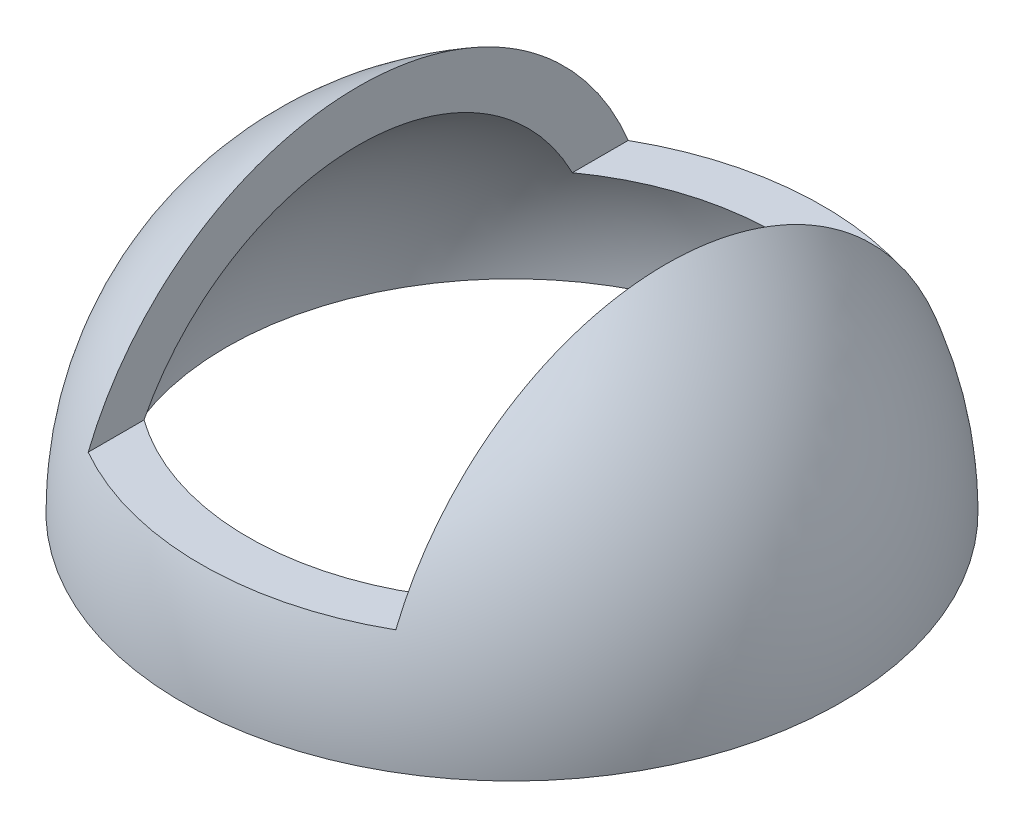
SolidWorks part; units mm, degrees
ref_plane "Front Plane" through (0, 0, 0) normal (0, 0, 1) x (1, 0, 0)
ref_plane "Top Plane" through (0, 0, 0) normal (0, 1, 0) x (1, 0, 0)
ref_plane "Right Plane" through (0, 0, 0) normal (1, 0, 0) x (0, 0, -1)
sketch "Sketch1" plane through (0, 0, 0) normal (0, 0, 1) x (1, 0, 0)
  line L0 (16.51, 0) -> (19.05, 0) construction
  line L1 (19.05, 0) -> (16.51, 0) construction
  line L2 (19.05, 0) -> (16.51, 0)
  line L3 (0, 19.05) -> (0, 16.51)
  arc A0 (19.05, 0) -> (0, 19.05) centre (0, 0) ccw
  arc A2 (16.51, 0) -> (0, 16.51) centre (0, 0) ccw
  circle A3 centre (0, 0) radius 19.05 construction
  circle A4 centre (0, 0) radius 16.51 construction
  dimension "D1" = 38.1
  dimension "D2" = 2.54
revolve "Revolve1" add sketch "Sketch1" angle 360 about L3
sketch "Sketch2" plane through (0, 0, 0) normal (0, 0, 1) x (1, 0, 0)
  line L0 (0, 6.35) -> (0, 0) construction
  line L1 (-8.89, 22.7688) -> (8.89, 22.7688)
  line L2 (-8.89, 22.7688) -> (-8.89, 6.35)
  line L3 (-8.89, 6.35) -> (8.89, 6.35)
  line L4 (8.89, 22.7688) -> (8.89, 6.35)
  dimension "D1" = 6.35
  dimension "D2" = 17.78
extrude "Cut-Extrude1" cut sketch "Sketch2" against normal mid plane 127
